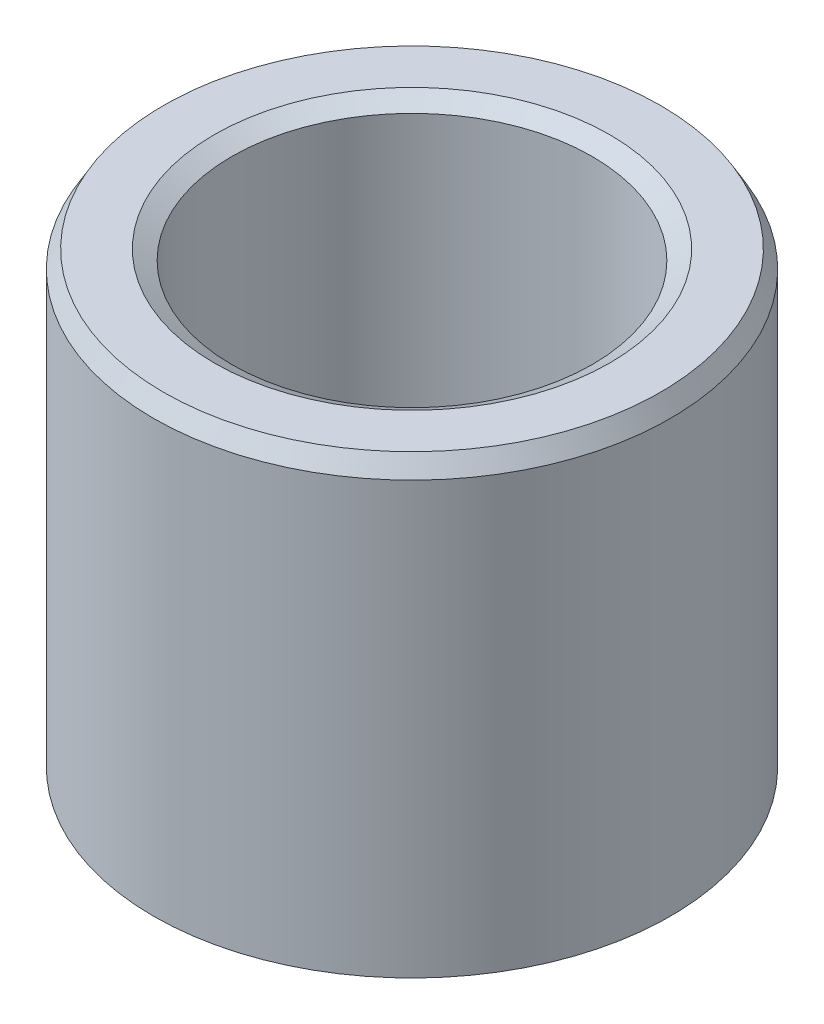
SolidWorks part; units mm, degrees
ref_plane "Front Plane" through (0, 0, 0) normal (0, 0, 1) x (1, 0, 0)
ref_plane "Top Plane" through (0, 0, 0) normal (0, 1, 0) x (1, 0, 0)
ref_plane "Right Plane" through (0, 0, 0) normal (1, 0, 0) x (0, 0, -1)
sketch "Sketch1" plane through (0, 0, 0) normal (0, 1, 0) x (1, 0, 0)
  circle A0 centre (0, 0) radius 42.5
  dimension "SLEEVE_OD" = 85
extrude "Boss-Extrude1" add sketch "Sketch1" along normal blind 75.4031
sketch "Sketch2" plane through (0, 0, 0) normal (0, 1, 0) x (1, 0, 0)
  circle A0 centre (0, 0) radius 29.6266
  dimension "BORE_D" = 59.2533
extrude "Cut-Extrude1" cut sketch "Sketch2" along normal through all
chamfer "Chamfer1" distance 2.8774 angle 30 4 edges at (0, 75.4031, 29.6266) (0, 0, 29.6266) (0, 0, 42.5) (0, 75.4031, 42.5) first distance on face at (0, 75.4031, 29.6266) first distance on face at (0, 0, 29.6266) first distance on face at (0, 75.4031, 42.5)
